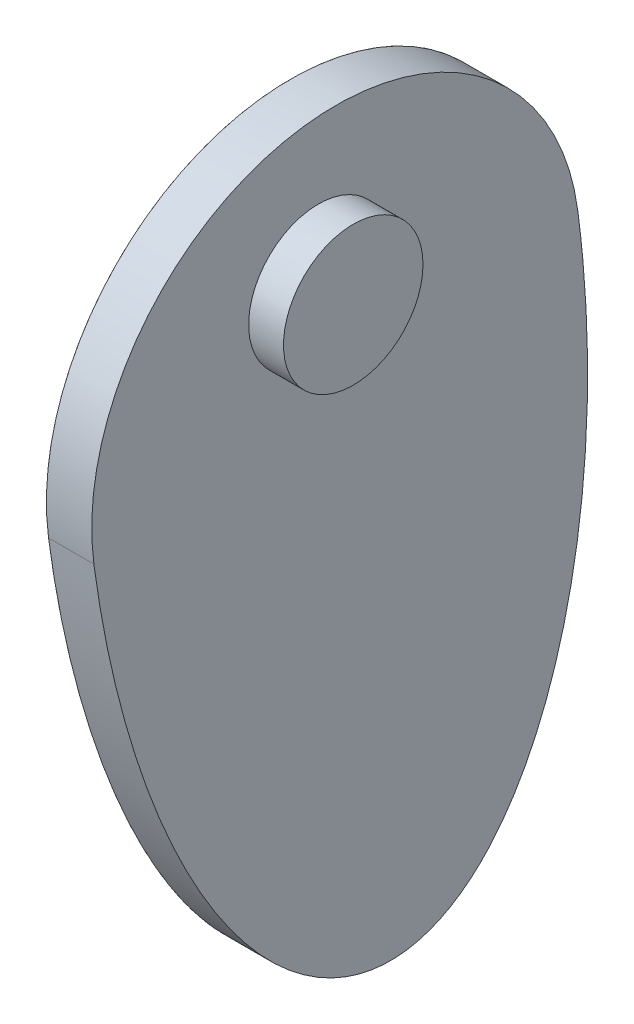
SolidWorks part; units mm, degrees
ref_plane "Plano frontal" through (0, 0, 0) normal (0, 0, 1) x (1, 0, 0)
ref_plane "Plano superior" through (0, 0, 0) normal (0, 1, 0) x (1, 0, 0)
ref_plane "Plano direito" through (0, 0, 0) normal (1, 0, 0) x (0, 0, -1)
sketch "Esboço43" plane through (0, 0, 0) normal (1, 0, 0) x (0, 0, -1)
  line L0 (0, 0) -> (0, -150) construction
  line L1 (0, -150) -> (20, -150) construction
  arc A0 (69.386, 9.2515) -> (-69.386, -9.2515) centre (0, 0) ccw
  ellipse E0 centre (0, 0) end of major axis (20, -150) minor radius 70 (-69.386, -9.2515) -> (69.386, 9.2515) ccw
  dimension "D1" = 140
  dimension "D2" = 150
  dimension "D3" = 20
extrude "Ressalto-extrusão11" add sketch "Esboço43" along normal blind 13
sketch3d "3DSketch4"
  arc A0 (13, 69.3586, 9.4543) -> (13, -149.9687, -20.2284) centre (-399.0364, -36.5209, -33.3487) cw
  arc A1 (13, 9.2515, -69.386) -> (13, -9.2515, 69.386) centre (13, 0, 0) ccw construction
  spline S0 degree 3 poles (13, -9.2515, 69.386) (13, -309.2515, 29.386) (13, -290.7485, -109.386) (13, 9.2515, -69.386) knots 0 0 0 0 1 1 1 1 weights 1 0.333333 0.333333 1 construction
  point P2 (-369.8245, 20.6877, -456.0665)
  point P8 (83, 0, 0)
surface "Superfície-Preenchimento3"
sketch "Esboço44" plane through (0, 0, 0) normal (1, 0, 0) x (0, 0, -1)
  line L0 (0, 70) -> (-25.8959, 70) construction
  circle A2 centre (-5, 28) radius 20
  spline S0 degree 3 poles (69.386, 9.2515) (69.3402, 9.5842) (69.2487, 10.2496) (69.0931, 11.2451) (68.9244, 12.2383) (68.741, 13.229) (68.5435, 14.217) (68.2109, 15.7648) (67.7009, 17.863) (66.9516, 20.4934) (65.8165, 23.9584) (64.1451, 28.2026) (62.1475, 32.3034) (59.9151, 36.2766) (56.9602, 40.8822) (53.5638, 45.1853) (49.234, 49.868) (45.2095, 53.5903) (40.8489, 56.8962) (37.0624, 59.4323) (33.1303, 61.7444) (29.0296, 63.7424) (24.8229, 65.4953) (20.5169, 67.0003) (16.1064, 68.1645) (11.6395, 69.0676) (7.1232, 69.7083) (2.5707, 69.9943) (-1.9867, 70.0133) (-7.4506, 69.7159) (-12.869, 68.8853) (-18.1923, 67.6377) (-22.565, 66.3386) (-26.8228, 64.7021) (-30.9737, 62.8208) (-35.011, 60.6977) (-38.8702, 58.266) (-42.5771, 55.6148) (-46.1256, 52.7486) (-49.4394, 49.6141) (-52.5613, 46.2939) (-56.0701, 42.0947) (-59.1579, 37.5653) (-61.8756, 32.821) (-64.3133, 27.9217) (-66.2647, 22.799) (-67.8063, 17.5533) (-68.8342, 13.109) (-69.5118, 8.5982) (-69.8414, 4.9669) (-69.9821, 2.2356) (-70.016, -0.4992) (-69.9434, -3.2333) (-69.7863, -5.6034) (-69.5935, -7.6093) (-69.4551, -8.7041) (-69.386, -9.2515) knots 0 0 0 0 0.004582 0.009165 0.013748 0.01833 0.022913 0.027495 0.039932 0.052369 0.064806 0.089675 0.114544 0.126981 0.15185 0.189142 0.201578 0.238871 0.263739 0.276177 0.301046 0.325914 0.338352 0.363221 0.38809 0.400527 0.425396 0.450265 0.462702 0.487571 0.524862 0.537299 0.562169 0.587037 0.599474 0.624344 0.649212 0.661649 0.686519 0.711387 0.723824 0.748694 0.785985 0.798423 0.823291 0.860583 0.87302 0.897889 0.922759 0.935195 0.947632 0.960069 0.972506 0.984943 0.992472 1 1 1 1 construction
  dimension "D1" = 40
  dimension "D3" = 42
  dimension "D2" = 5
  dimension "D4" = 70
extrude "Ressalto-extrusão12" add sketch "Esboço44" against normal blind 10
ref_plane "Plano1" through (-50, 0, 0) normal (1, 0, 0) x (0, 0, -1)
mirror "Espelhar3" about plane through (-50, 0, 0) normal (1, 0, 0) of bodies 118 117
delete or keep bodies "Corpo-Excluir/Manter 1" type delete bodies bodies 117 118
